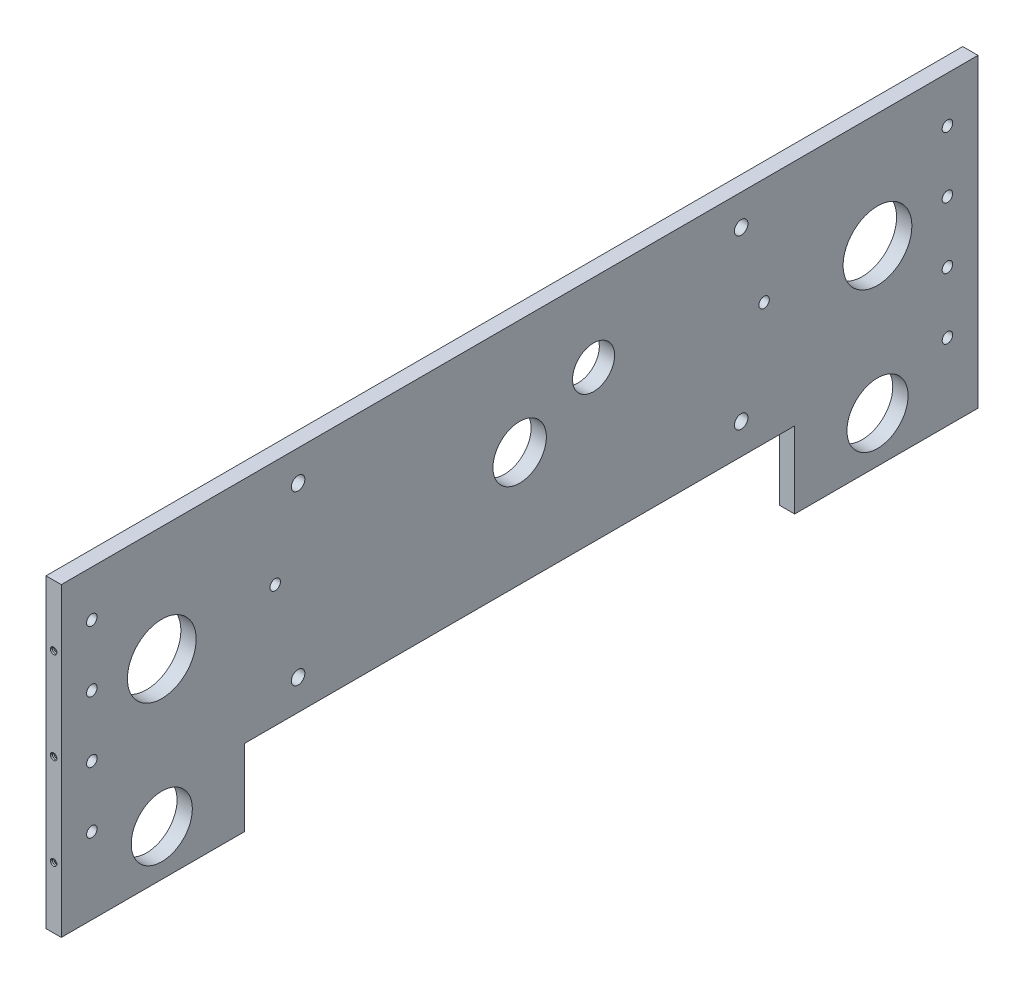
SolidWorks part; units mm, degrees
material "6061-T6 (SS)"
ref_plane "Front Plane" through (0, 0, 0) normal (0, 0, 1) x (1, 0, 0)
ref_plane "Top Plane" through (0, 0, 0) normal (0, 1, 0) x (1, 0, 0)
ref_plane "Right Plane" through (0, 0, 0) normal (1, 0, 0) x (0, 0, -1)
sketch "Sketch1" plane through (0, 0, 0) normal (1, 0, 0) x (0, 0, -1)
  line L1 (-190.5, 63.5) -> (190.5, 63.5)
  line L2 (-190.5, 63.5) -> (-190.5, -63.5)
  line L3 (-190.5, -63.5) -> (190.5, -63.5)
  line L4 (190.5, 63.5) -> (190.5, -63.5)
  line L5 (-190.5, 63.5) -> (190.5, -63.5) construction
  line L6 (-190.5, -63.5) -> (190.5, 63.5) construction
  point P0 (0, 0)
  dimension "D1" = 127
  dimension "D2" = 381
extrude "Boss-Extrude1" add sketch "Sketch1" along normal blind 6.35
sketch "Sketch2" plane through (6.35, 0, 0) normal (1, 0, 0) x (0, 0, -1)
  line L0 (-190.5, -63.5) -> (190.5, -63.5) construction
  line L1 (-148.7297, 15.875) -> (0, 15.875) construction
  line L2 (-74.3648, -34.925) -> (-74.3648, 15.875) construction
  line L3 (0, 15.875) -> (148.7297, 15.875) construction
  line L4 (74.3648, -34.925) -> (74.3648, 15.875) construction
  line L5 (190.5, 63.5) -> (-190.5, 63.5) construction
  line L6 (65.278, 53.34) -> (-56.642, 53.34) construction
  line L7 (65.278, 53.34) -> (65.278, -13.97) construction
  line L8 (65.278, -13.97) -> (-56.642, -13.97) construction
  line L9 (-56.642, 53.34) -> (-56.642, -13.97) construction
  line L10 (-190.5, -63.5) -> (190.5, -63.5) construction
  circle A1 centre (-148.7297, 15.875) radius 14.2875
  circle A2 centre (148.7297, 15.875) radius 14.2875
  circle A3 centre (-148.7297, 15.875) radius 38.1 construction
  circle A4 centre (0, 15.875) radius 38.1 construction
  circle A5 centre (148.7297, 15.875) radius 38.1 construction
  circle A6 centre (-74.3648, -34.925) radius 6.35 construction
  circle A7 centre (74.3648, -34.925) radius 6.35 construction
  circle A8 centre (-74.3648, 9.525) radius 6.35 construction
  circle A9 centre (74.3648, 9.525) radius 6.35 construction
  circle A11 centre (-148.7297, -44.4161) radius 12.7
  circle A12 centre (148.7297, -44.4161) radius 12.7
  circle A13 centre (0, 15.875) radius 29.2138 construction
  circle A14 centre (30.7215, 31.115) radius 5.08 construction
  circle A15 centre (30.7215, 31.115) radius 8.75
  circle A16 centre (0, 15.875) radius 11.1125
  point P11 (0, 0)
  dimension "D1" = 28.575
  dimension "D5" = 76.2
  dimension "D7" = 12.7
  dimension "D14" = 25.4
  dimension "D15" = 19.0839
  dimension "D17" = 25.4
  dimension "D20" = 58.4276
  dimension "D21" = 10.16
  dimension "D22" = 17.5001
  dimension "D24" = 22.225
  dimension "D25" = 28.575
  dimension "D2" = 79.375
  dimension "D3" = 148.7297
  dimension "D4" = 148.7297
  dimension "D6" = 0
  dimension "D8" = 28.575
  dimension "D9" = 44.45
  dimension "D10" = 56.642
  dimension "D11" = 121.92
  dimension "D12" = 10.16
  dimension "D13" = 49.53
  dimension "D16" = 148.7297
  dimension "D18" = 19.0839
  dimension "D19" = 148.7297
  dimension "D23" = 15.24
extrude "Cut-Extrude1" cut sketch "Sketch2" against normal through all
sketch "Sketch3" plane through (6.35, 0, 0) normal (1, 0, 0) x (0, 0, -1)
  line L0 (-184.404, 19.05) -> (-184.404, -19.05) construction
  line L1 (-190.5, 63.5) -> (-190.5, -63.5) construction
  point P2 (-184.404, 0)
  point P3 (-190.5, 0)
  dimension "D1" = 38.1
  dimension "D2" = 6.096
sketch "Sketch23" plane through (6.35, 0, 0) normal (1, 0, 0) x (0, 0, -1)
  line L0 (-114.3, -63.5) -> (-114.3, -31.75)
  line L1 (-190.5, -63.5) -> (190.5, -63.5) construction
  line L2 (-114.3, -31.75) -> (114.3, -31.75)
  line L3 (114.3, -31.75) -> (114.3, -63.5)
  line L4 (-190.5, 63.5) -> (-190.5, -63.5) construction
  line L5 (190.5, -63.5) -> (190.5, 63.5) construction
  line L6 (-114.3, -63.5) -> (114.3, -63.5)
  dimension "D1" = 31.75
  dimension "D2" = 76.2
  dimension "D3" = 76.2
extrude "Cut-Extrude6" cut sketch "Sketch23" against normal through all
sketch "Sketch24" plane through (0, 0, 0) normal (-1, 0, 0) x (0, 0, 1)
  line L0 (-190.5, -63.5) -> (-190.5, 63.5) construction
  line L1 (-190.5, 63.5) -> (190.5, 63.5) construction
  point P0 (-92.075, -19.05)
  point P1 (-92.075, 50.8)
  point P2 (92.075, -19.05)
  point P4 (92.075, 50.8)
  dimension "D1" = 69.85
  dimension "D2" = 98.425
  dimension "D3" = 12.7
  dimension "D4" = 12.7
  dimension "D5" = 69.85
  dimension "D6" = 184.15
hole_wizard "CSK for #10 Flat Head Machine Screw2" positions "Sketch25" profile "Sketch26" countersink size "#10" standard "ANSI Inch" end condition through all
sketch "Sketch25" plane through (0, 0, 0) normal (-1, 0, 0) x (0, 0, 1)
  point P0 (-92.075, 50.8)
  point P3 (-92.075, -19.05)
  point P6 (92.075, -19.05)
  point P9 (92.075, 50.8)
sketch "Sketch26" plane through (0, 50.8, -92.075) normal (0, 1, 0) x (0, 0, 1)
  line L0 (0, 0) -> (0, 6.35)
  line L1 (0, 6.35) -> (2.8067, 6.35)
  line L2 (2.8067, 6.35) -> (2.8067, 2.396)
  line L3 (2.8067, 2.396) -> (4.8895, 0)
  line L5 (4.8895, 0) -> (0, 0)
  line L6 (-2.8067, 2.396) -> (-4.8895, 0) construction
  line L11 (0, -6.35) -> (0, 107.95) construction
  dimension "Thru Hole Dia." = 5.6134
  dimension "Thru Hole Depth" = 6.35
  dimension "Near C'Sink Dia." = 9.779
  dimension "Near C'Sink Angle" = 82
sketch "Sketch27" plane through (6.35, 0, 0) normal (1, 0, 0) x (0, 0, -1)
  line L0 (190.5, -63.5) -> (190.5, 63.5) construction
  line L1 (114.3, -63.5) -> (190.5, -63.5) construction
  line L2 (-190.5, -63.5) -> (-114.3, -63.5) construction
  line L3 (-190.5, 63.5) -> (-190.5, -63.5) construction
  point P0 (177.8, -57.15)
  point P1 (177.8, -31.75)
  point P2 (177.8, -6.35)
  point P3 (177.8, 19.05)
  point P4 (177.8, 44.45)
  point P7 (-177.8, -57.15)
  point P8 (-177.8, -31.75)
  point P9 (-177.8, -6.35)
  point P10 (-177.8, 19.05)
  point P11 (-177.8, 44.45)
  dimension "D1" = 25.4
  dimension "D2" = 25.4
  dimension "D3" = 25.4
  dimension "D4" = 25.4
  dimension "D5" = 12.7
  dimension "D6" = 25.4
  dimension "D7" = 25.4
  dimension "D8" = 25.4
  dimension "D9" = 25.4
  dimension "D10" = 6.35
  dimension "D11" = 6.35
  dimension "D12" = 12.7
hole_wizard "11/64 (0.17188) Diameter Hole1" positions "Sketch28" profile "Sketch29" hole size "11/64" standard "ANSI Inch" end condition through all
sketch "Sketch28" plane through (6.35, 0, 0) normal (1, 0, 0) x (0, 0, -1)
  point P0 (-177.8, 44.45)
  point P3 (-177.8, 19.05)
  point P6 (-177.8, -6.35)
  point P9 (-177.8, -31.75)
  point P12 (177.8, -31.75)
  point P15 (177.8, -6.35)
  point P18 (177.8, 19.05)
  point P21 (177.8, 44.45)
sketch "Sketch29" plane through (6.35, 44.45, 177.8) normal (0, 1, 0) x (0, 0, -1)
  line L0 (0, 0) -> (0, 6.35)
  line L1 (0, 6.35) -> (2.1829, 6.35)
  line L2 (2.1829, 6.35) -> (2.1829, 0)
  line L5 (2.1829, 0) -> (0, 0)
  line L11 (0, -6.35) -> (0, 107.95) construction
  dimension "Thru Hole Dia." = 4.3658
  dimension "Thru Hole Depth" = 6.35
sketch "Sketch30" plane through (6.35, 0, 0) normal (1, 0, 0) x (0, 0, -1)
  line L0 (-190.5, 63.5) -> (-190.5, -63.5) construction
  line L1 (190.5, -63.5) -> (190.5, 63.5) construction
  line L2 (190.5, 63.5) -> (-190.5, 63.5) construction
  point P0 (-101.6, 19.05)
  point P1 (101.6, 19.05)
  dimension "D1" = 88.9
  dimension "D2" = 88.9
  dimension "D3" = 44.45
hole_wizard "11/64 (0.17188) Diameter Hole2" positions "Sketch31" profile "Sketch32" hole size "11/64" standard "ANSI Inch"
sketch "Sketch31" plane through (6.35, 0, 0) normal (1, 0, 0) x (0, 0, -1)
  point P0 (-101.6, 19.05)
  point P3 (101.6, 19.05)
sketch "Sketch32" plane through (6.35, 19.05, 101.6) normal (0, 1, 0) x (0, 0, -1)
  line L0 (0, 0) -> (0, 10.2016)
  line L1 (0, 10.2016) -> (2.1829, 8.89)
  line L2 (2.1829, 8.89) -> (2.1829, 0)
  line L5 (2.1829, 0) -> (0, 0)
  line L10 (0, 10.2016) -> (-2.1829, 8.89) construction
  line L11 (0, -6.35) -> (0, 107.95) construction
  dimension "Hole Dia." = 4.3658
  dimension "Hole Depth" = 8.89
  dimension "Drill Angle" = 118
sketch "Sketch33" plane through (0, 0, 190.5) normal (0, 0, 1) x (1, 0, 0)
  line L0 (6.35, 63.5) -> (0, 63.5) construction
  line L1 (0, 63.5) -> (0, -63.5) construction
  point P0 (3.175, 38.1)
  point P1 (3.175, 0)
  point P2 (3.175, -38.1)
  dimension "D1" = 25.4
  dimension "D2" = 3.175
  dimension "D3" = 38.1
  dimension "D4" = 38.1
hole_wizard "#36 (0.1065) Diameter Hole1" positions "Sketch34" profile "Sketch35" hole size "#36" standard "ANSI Inch"
sketch "Sketch34" plane through (0, 0, 190.5) normal (0, 0, 1) x (1, 0, 0)
  point P0 (3.175, 38.1)
  point P3 (3.175, -38.1)
  point P6 (3.175, 0)
sketch "Sketch35" plane through (3.175, 38.1, 190.5) normal (1, 0, 0) x (0, -1, 0)
  line L0 (0, 0) -> (0, 9.7027)
  line L1 (0, 9.7027) -> (1.3525, 8.89)
  line L2 (1.3525, 8.89) -> (1.3525, 0)
  line L5 (1.3525, 0) -> (0, 0)
  line L10 (0, 9.7027) -> (-1.3525, 8.89) construction
  line L11 (0, -6.35) -> (0, 107.95) construction
  dimension "Hole Dia." = 2.7051
  dimension "Hole Depth" = 8.89
  dimension "Drill Angle" = 118
thread "Thread1" pitch 0.7937 method cut profile "Thread Profile1" start angle 0, offset 0, length 6.35, pitch 0.7937, diameter 2.7051
ref_plane "Plane1" through (1.8225, 38.1, 190.5) normal (0, -1, 0) x (-1, 0, 0)
sketch "Thread Profile1" plane through (1.8225, 38.1, 190.5) normal (0, -1, 0) x (-1, 0, 0)
  line L0 (0, 0) -> (0, 0.7937) construction
  line L1 (0, 0) -> (0.4296, 0.248)
  line L2 (0.4296, 0.248) -> (0.4296, 0.3473)
  line L3 (0.4296, 0.3473) -> (0, 0.5953)
  line L4 (0.4296, 0.2977) -> (0, 0.2977) construction
  line L11 (0, 0) -> (0, 0.5953)
  point P2 (0, 0)
  dimension "Pitch" = 0.7937
  dimension "Profile_Angle" = 60
  dimension "Profile_Land" = 0.0992
  dimension "Profile_Height" = 0.4296
thread "Thread2" pitch 0.7937 method cut profile "Thread Profile2" start angle 0, offset 0, length 6.35, pitch 0.7937, diameter 2.7051
ref_plane "Plane2" through (1.8225, 0, 190.5) normal (0, -1, 0) x (-1, 0, 0)
sketch "Thread Profile2" plane through (1.8225, 0, 190.5) normal (0, -1, 0) x (-1, 0, 0)
  line L0 (0, 0) -> (0, 0.7937) construction
  line L1 (0, 0) -> (0.4296, 0.248)
  line L2 (0.4296, 0.248) -> (0.4296, 0.3473)
  line L3 (0.4296, 0.3473) -> (0, 0.5953)
  line L4 (0.4296, 0.2977) -> (0, 0.2977) construction
  line L11 (0, 0) -> (0, 0.5953)
  point P2 (0, 0)
  dimension "Pitch" = 0.7937
  dimension "Profile_Angle" = 60
  dimension "Profile_Land" = 0.0992
  dimension "Profile_Height" = 0.4296
thread "Thread3" pitch 0.7937 method cut profile "Thread Profile3" start angle 0, offset 0, length 6.35, pitch 0.7937, diameter 2.7051
ref_plane "Plane3" through (1.8225, -38.1, 190.5) normal (0, -1, 0) x (-1, 0, 0)
sketch "Thread Profile3" plane through (1.8225, -38.1, 190.5) normal (0, -1, 0) x (-1, 0, 0)
  line L0 (0, 0) -> (0, 0.7937) construction
  line L1 (0, 0) -> (0.4296, 0.248)
  line L2 (0.4296, 0.248) -> (0.4296, 0.3473)
  line L3 (0.4296, 0.3473) -> (0, 0.5953)
  line L4 (0.4296, 0.2977) -> (0, 0.2977) construction
  line L11 (0, 0) -> (0, 0.5953)
  point P2 (0, 0)
  dimension "Pitch" = 0.7937
  dimension "Profile_Angle" = 60
  dimension "Profile_Land" = 0.0992
  dimension "Profile_Height" = 0.4296
sketch "Sketch42" plane through (0, 0, -190.5) normal (0, 0, -1) x (-1, 0, 0)
  line L0 (-6.35, 63.5) -> (0, 63.5) construction
  line L2 (-6.35, -63.5) -> (-6.35, 63.5) construction
  point P0 (-3.175, 38.1)
  point P1 (-3.175, 0)
  point P2 (-3.175, -38.1)
  dimension "D1" = 25.4
  dimension "D2" = 3.175
hole_wizard "#36 (0.1065) Diameter Hole2" positions "Sketch43" profile "Sketch44" hole size "#36" standard "ANSI Inch"
sketch "Sketch43" plane through (0, 0, -190.5) normal (0, 0, -1) x (-1, 0, 0)
  point P0 (-3.175, 38.1)
  point P3 (-3.175, 0)
  point P6 (-3.175, -38.1)
sketch "Sketch44" plane through (3.175, 38.1, -190.5) normal (1, 0, 0) x (0, 1, 0)
  line L0 (0, 0) -> (0, 9.7027)
  line L1 (0, 9.7027) -> (1.3525, 8.89)
  line L2 (1.3525, 8.89) -> (1.3525, 0)
  line L5 (1.3525, 0) -> (0, 0)
  line L10 (0, 9.7027) -> (-1.3525, 8.89) construction
  line L11 (0, -6.35) -> (0, 107.95) construction
  dimension "Hole Dia." = 2.7051
  dimension "Hole Depth" = 8.89
  dimension "Drill Angle" = 118
thread "Thread4" pitch 0.7937 method cut profile "Thread Profile4" start angle 0, offset 0, length 6.35, pitch 0.7937, diameter 2.7051
ref_plane "Plane4" through (4.5275, 38.1, -190.5) normal (0, -1, 0) x (1, 0, 0)
sketch "Thread Profile4" plane through (4.5275, 38.1, -190.5) normal (0, -1, 0) x (1, 0, 0)
  line L0 (0, 0) -> (0, 0.7937) construction
  line L1 (0, 0) -> (0.4296, 0.248)
  line L2 (0.4296, 0.248) -> (0.4296, 0.3473)
  line L3 (0.4296, 0.3473) -> (0, 0.5953)
  line L4 (0.4296, 0.2977) -> (0, 0.2977) construction
  line L11 (0, 0) -> (0, 0.5953)
  point P2 (0, 0)
  dimension "Pitch" = 0.7937
  dimension "Profile_Angle" = 60
  dimension "Profile_Land" = 0.0992
  dimension "Profile_Height" = 0.4296
thread "Thread5" pitch 0.7937 method cut profile "Thread Profile5" start angle 0, offset 0, length 6.35, pitch 0.7937, diameter 2.7051
ref_plane "Plane5" through (4.5275, 0, -190.5) normal (0, -1, 0) x (1, 0, 0)
sketch "Thread Profile5" plane through (4.5275, 0, -190.5) normal (0, -1, 0) x (1, 0, 0)
  line L0 (0, 0) -> (0, 0.7937) construction
  line L1 (0, 0) -> (0.4296, 0.248)
  line L2 (0.4296, 0.248) -> (0.4296, 0.3473)
  line L3 (0.4296, 0.3473) -> (0, 0.5953)
  line L4 (0.4296, 0.2977) -> (0, 0.2977) construction
  line L11 (0, 0) -> (0, 0.5953)
  point P2 (0, 0)
  dimension "Pitch" = 0.7937
  dimension "Profile_Angle" = 60
  dimension "Profile_Land" = 0.0992
  dimension "Profile_Height" = 0.4296
thread "Thread6" pitch 0.7937 method cut profile "Thread Profile6" start angle 0, offset 0, length 6.35, pitch 0.7937, diameter 2.7051
ref_plane "Plane6" through (4.5275, -38.1, -190.5) normal (0, -1, 0) x (1, 0, 0)
sketch "Thread Profile6" plane through (4.5275, -38.1, -190.5) normal (0, -1, 0) x (1, 0, 0)
  line L0 (0, 0) -> (0, 0.7937) construction
  line L1 (0, 0) -> (0.4296, 0.248)
  line L2 (0.4296, 0.248) -> (0.4296, 0.3473)
  line L3 (0.4296, 0.3473) -> (0, 0.5953)
  line L4 (0.4296, 0.2977) -> (0, 0.2977) construction
  line L11 (0, 0) -> (0, 0.5953)
  point P2 (0, 0)
  dimension "Pitch" = 0.7937
  dimension "Profile_Angle" = 60
  dimension "Profile_Land" = 0.0992
  dimension "Profile_Height" = 0.4296
